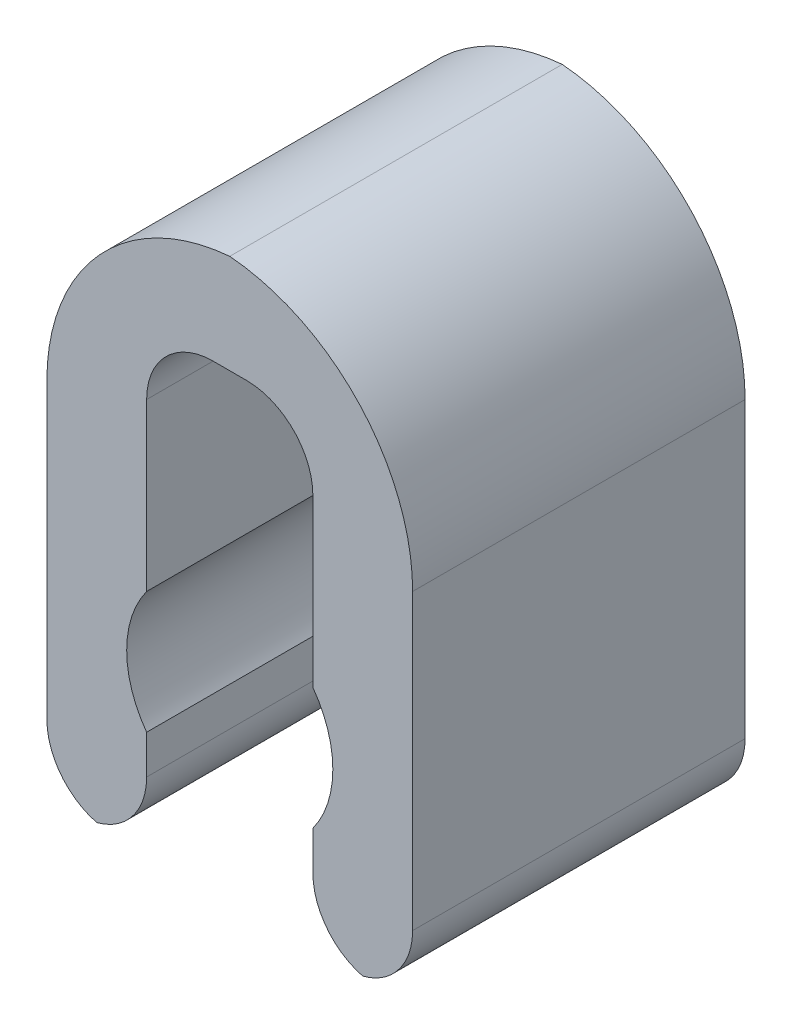
SolidWorks part; units mm, degrees
ref_plane "Front Plane" through (0, 0, 0) normal (0, 0, 1) x (1, 0, 0)
ref_plane "Top Plane" through (0, 0, 0) normal (0, 1, 0) x (1, 0, 0)
ref_plane "Right Plane" through (0, 0, 0) normal (1, 0, 0) x (0, 0, -1)
sketch "Sketch1" plane through (0, 0, 0) normal (0, 0, 1) x (1, 0, 0)
  line L0 (-27.1712, -6.1809) -> (-27.1712, -9.3479)
  line L1 (-27.1712, -2.5149) -> (-22.1712, -2.5149)
  line L2 (-27.1712, -2.5149) -> (-27.1712, 4.4851)
  line L3 (-27.1712, 4.4851) -> (-22.1712, 4.4851)
  line L4 (-22.1712, -2.5149) -> (-22.1712, 4.4851)
  line L5 (-30.1712, 7.4851) -> (-19.1712, 7.4851)
  line L6 (-30.1712, 7.4851) -> (-30.1712, -9.3479)
  line L7 (-30.1712, -9.3479) -> (-19.1712, -9.3479)
  line L8 (-19.1712, 7.4851) -> (-19.1712, -9.3479)
  line L9 (-22.1712, -6.1809) -> (-22.1712, -9.3479)
  circle A0 centre (-24.6712, -4.3479) radius 3.1
  dimension "D1" = 6.2
  dimension "D2" = 5
  dimension "D3" = 7
  dimension "D4" = 3
  dimension "D5" = 3
  dimension "D6" = 3
  dimension "D7" = 5
  dimension "D8" = 5.5
extrude "Boss-Extrude1" add sketch "Sketch1" along normal blind 10 contours A0 L9 L7 L8 L5 L6 L0 L2 L3 L4 region at (-27.3723, -7.7644, 0)
fillet "Fillet1" radius 6 2 edges at (-19.1712, 7.4851, 5) (-30.1712, 7.4851, 5)
fillet "Fillet2" radius 2 4 edges at (-19.1712, -9.3479, 5) (-22.1712, -9.3479, 5) (-27.1712, -9.3479, 5) (-30.1712, -9.3479, 5)
fillet "Fillet3" radius 2 2 edges at (-27.1712, 4.4851, 5) (-22.1712, 4.4851, 5)
